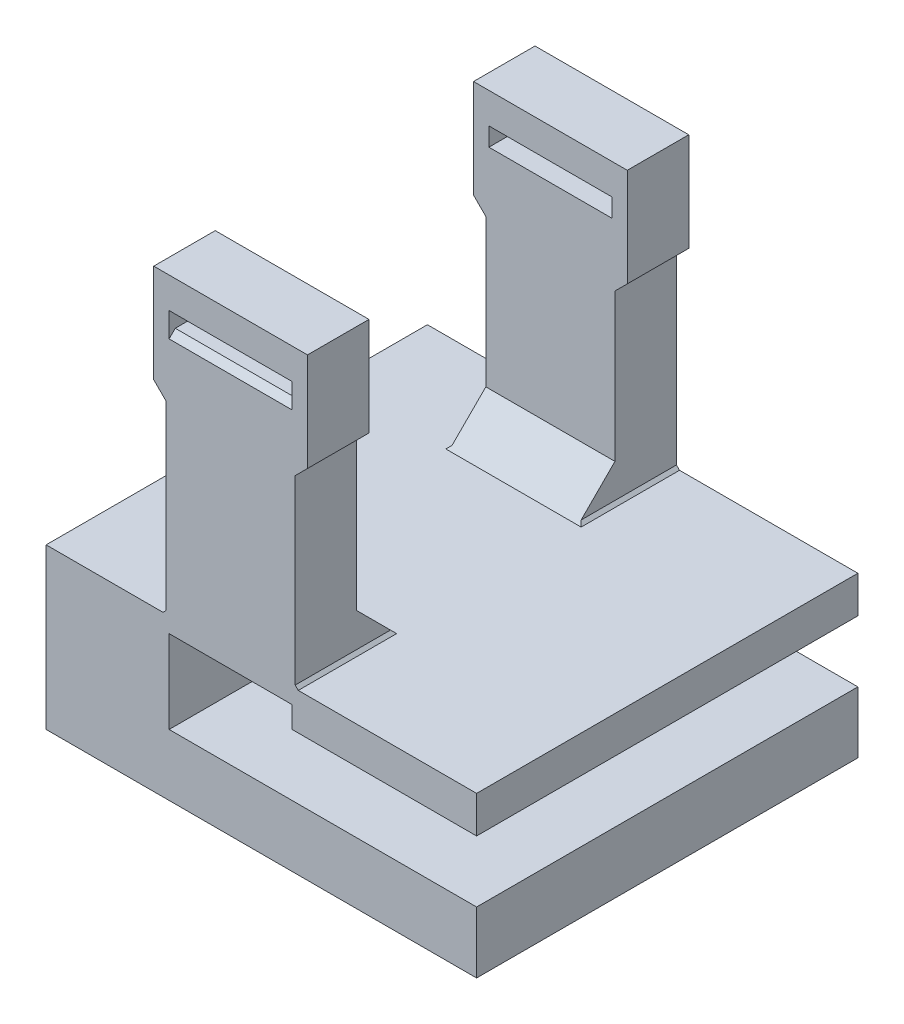
SolidWorks part; units mm, degrees
ref_plane "Plano frontal" through (0, 0, 0) normal (0, 0, 1) x (1, 0, 0)
ref_plane "Plano superior" through (0, 0, 0) normal (0, 1, 0) x (1, 0, 0)
ref_plane "Plano direito" through (0, 0, 0) normal (1, 0, 0) x (0, 0, -1)
sketch "Esboço1" plane through (0, 0, 0) normal (0, 1, 0) x (1, 0, 0)
  line L1 (10.5, -21) -> (-10.5, -21) construction
  line L2 (10.5, -21) -> (10.5, 21) construction
  line L3 (10.5, 21) -> (-10.5, 21) construction
  line L4 (-10.5, -21) -> (-10.5, 21) construction
  line L5 (10.5, -21) -> (-10.5, 21) construction
  line L6 (10.5, 21) -> (-10.5, -21) construction
  line L7 (20, -31) -> (-20, -31)
  line L8 (20, -31) -> (20, 31)
  line L9 (20, 31) -> (-20, 31)
  line L10 (-20, -31) -> (-20, 31)
  line L11 (20, -31) -> (-20, 31) construction
  line L12 (20, 31) -> (-20, -31) construction
  point P0 (0, 0)
  point P6 (0, 0)
  dimension "D1" = 42
  dimension "D2" = 21
  dimension "D3" = 10
  dimension "D4" = 40
extrude "Ressalto-extrusão1" add sketch "Esboço1" along normal blind 6
sketch "Esboço2" plane through (0, 6, 0) normal (0, 1, 0) x (1, 0, 0)
  line L0 (10.5, 21) -> (-10.5, 21) construction
  line L1 (10.5, -21) -> (-10.5, -21)
  line L2 (10.5, -21) -> (10.5, 21) construction
  line L3 (10.5, 21) -> (-10.5, 21)
  line L4 (-10.5, -21) -> (-10.5, 21) construction
  line L5 (10.5, -21) -> (-10.5, 21) construction
  line L6 (10.5, 21) -> (-10.5, -21) construction
  line L7 (-10.5, 21) -> (-10.5, 31)
  line L8 (20, 31) -> (-20, 31) construction
  line L9 (-10.5, 31) -> (10.5, 31)
  line L10 (10.5, 31) -> (10.5, 21)
  line L11 (10.5, -21) -> (10.5, -31)
  line L12 (20, -31) -> (-20, -31) construction
  line L13 (10.5, -31) -> (-10.5, -31)
  line L14 (-10.5, -31) -> (-10.5, -21)
  point P0 (0, 0)
extrude "Ressalto-extrusão2" add sketch "Esboço2" along normal blind 48
chamfer "Chanfro1" distance 6 angle 45 2 edges at (0, 6, 21) (0, 6, -21)
sketch "Esboço3" plane through (0, 0, 0) normal (0, -1, 0) x (1, 0, 0)
  line L0 (20, -31) -> (-20, -31) construction
  line L1 (-10, 31) -> (-20, 31)
  line L2 (-10, 31) -> (-10, -31)
  line L3 (-10, -31) -> (-20, -31)
  line L4 (-20, 31) -> (-20, -31)
  dimension "D1" = 10
extrude "Ressalto-extrusão3" add sketch "Esboço3" along normal blind 20
sketch "Esboço4" plane through (-10, 0, 0) normal (1, 0, 0) x (0, 0, -1)
  line L0 (31, -20) -> (31, 0) construction
  line L1 (-31, -20) -> (31, -20)
  line L2 (-31, -20) -> (-31, -10)
  line L3 (-31, -10) -> (31, -10)
  line L4 (31, -20) -> (31, -10)
  line L5 (31, 0) -> (-31, 0) construction
  dimension "D1" = 10
extrude "Ressalto-extrusão4" add sketch "Esboço4" along normal blind 50
sketch "Esboço5" plane through (0, 0, 31) normal (0, 0, 1) x (1, 0, 0)
  line L0 (-20, 6) -> (-10.5, 6) construction
  line L7 (-10.5, 54) -> (-12.5, 54)
  line L8 (-10.5, 54) -> (-10.5, 41)
  line L9 (-10.5, 41) -> (-12.5, 41)
  line L10 (-12.5, 54) -> (-12.5, 41)
  line L11 (10.5, 54) -> (12.5, 54)
  line L12 (10.5, 54) -> (10.5, 41)
  line L13 (10.5, 41) -> (12.5, 41)
  line L14 (12.5, 54) -> (12.5, 41)
  dimension "D1" = 25
  dimension "D2" = 35
extrude "Ressalto-extrusão5" add sketch "Esboço5" against normal blind 10
mirror "Espelhar1" about plane through (0, 0, 0) normal (0, 0, 1) of "Ressalto-extrusão5"
sketch "Esboço6" plane through (0, 0, 31) normal (0, 0, 1) x (1, 0, 0)
  line L0 (0, 54) -> (0, 0) construction
  line L1 (-12.5, 54) -> (12.5, 54) construction
  line L2 (-20, 6) -> (-10.5, 6) construction
  line L3 (10, 46) -> (-10, 46)
  line L4 (10, 46) -> (10, 49)
  line L5 (10, 49) -> (-10, 49)
  line L6 (-10, 46) -> (-10, 49)
  line L7 (10, 46) -> (-10, 49) construction
  line L8 (10, 49) -> (-10, 46) construction
  line L10 (-10, 0) -> (10, 0)
  line L11 (-10, 0) -> (-10, 2.5)
  line L12 (-10, 2.5) -> (10, 2.5)
  line L13 (10, 0) -> (10, 2.5)
  line L14 (-10, 0) -> (20, 0) construction
  point P5 (0, 47.5)
  dimension "D1" = 20
  dimension "D2" = 3
  dimension "D3" = 40
  dimension "D4" = 2.5
extrude "Corte-extrusão1" cut sketch "Esboço6" against normal through all
chamfer "Chanfro2" distance 1 angle 45 4 edges at (0, 46, -31) (0, 46, 31) (0, 2.5, -31) (0, 2.5, 31)
chamfer "Chanfro3" distance 5 angle 45 4 edges at (-10.5, 41, -26) (10.5, 41, -26) (10.5, 41, 26) (-10.5, 41, 26)
sketch "Esboço7" plane through (-20, 0, 0) normal (-1, 0, 0) x (0, 0, 1)
  line L4 (-31, 6) -> (-31, -20)
  line L5 (-31, -20) -> (31, -20)
  line L6 (31, -20) -> (31, 6)
  line L7 (31, 6) -> (-31, 6)
  line L8 (-31, 6) -> (-31, -20)
  line L9 (-31, -20) -> (31, -20)
  line L10 (31, -20) -> (31, 6)
  line L11 (31, 6) -> (-31, 6)
  dimension "D1" = 0
extrude "Ressalto-extrusão6" add sketch "Esboço7" along normal offset from surface (10 mm away) 20 up to face at (-10, -1.3333, 0)
chamfer "Chanfro4" distance 0.5 angle 45 4 edges at (-10.5, 6, 23) (-10.5, 6, -23) (10.5, 6, -23) (10.5, 6, 23)
sketch "Esboço8" plane through (20, 0, 0) normal (1, 0, 0) x (0, 0, -1)
  line L4 (-31, 0) -> (31, 0)
  line L5 (31, 0) -> (31, 6)
  line L6 (31, 6) -> (-31, 6)
  line L7 (-31, 6) -> (-31, 0)
  line L8 (-31, 0) -> (31, 0)
  line L9 (31, 0) -> (31, 6)
  line L10 (31, 6) -> (-31, 6)
  line L11 (-31, 6) -> (-31, 0)
  dimension "D1" = 0
extrude "Ressalto-extrusão7" add sketch "Esboço8" along normal blind 20
